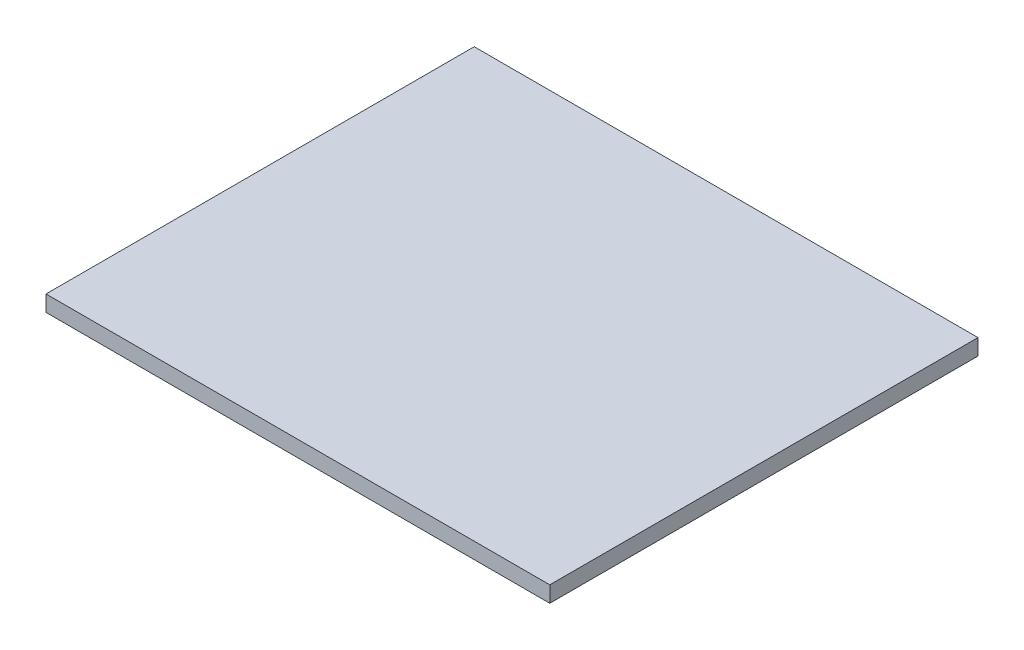
SolidWorks part; units mm, degrees
material "AISI 304"
ref_plane "Front Plane" through (0, 0, 0) normal (0, 0, 1) x (1, 0, 0)
ref_plane "Top Plane" through (0, 0, 0) normal (0, 1, 0) x (1, 0, 0)
ref_plane "Right Plane" through (0, 0, 0) normal (1, 0, 0) x (0, 0, -1)
sketch "Sketch1" plane through (0, 0, 0) normal (0, 1, 0) x (1, 0, 0)
  line L1 (-100, -85) -> (100, -85)
  line L2 (-100, -85) -> (-100, 85)
  line L3 (-100, 85) -> (100, 85)
  line L4 (100, -85) -> (100, 85)
  line L5 (-100, -85) -> (100, 85) construction
  line L6 (-100, 85) -> (100, -85) construction
  point P0 (0, 0)
  dimension "D1" = 200
  dimension "D2" = 170
extrude "1/4\" Steel Plate" add sketch "Sketch1" along normal blind 6.35
